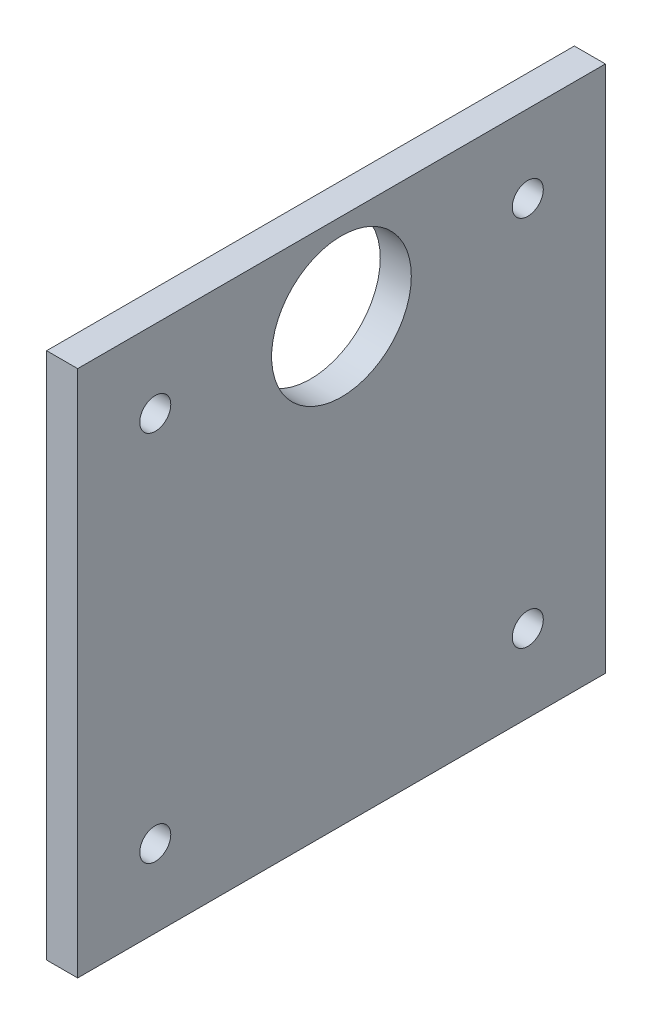
SolidWorks part; units mm, degrees
material "1060 Alloy"
ref_plane "Front Plane" through (0, 0, 0) normal (0, 0, 1) x (1, 0, 0)
ref_plane "Top Plane" through (0, 0, 0) normal (0, 1, 0) x (1, 0, 0)
ref_plane "Right Plane" through (0, 0, 0) normal (1, 0, 0) x (0, 0, -1)
sketch "Sketch1" plane through (0, 0, 0) normal (1, 0, 0) x (0, 0, -1)
  line L1 (-53.975, -53.975) -> (53.975, -53.975)
  line L2 (-53.975, -53.975) -> (-53.975, 53.975)
  line L3 (-53.975, 53.975) -> (53.975, 53.975)
  line L4 (53.975, -53.975) -> (53.975, 53.975)
  line L5 (-53.975, -53.975) -> (53.975, 53.975) construction
  line L6 (-53.975, 53.975) -> (53.975, -53.975) construction
  circle A0 centre (-0.0121, 36.2388) radius 14.2875
  circle A1 centre (-38.1, 38.1) radius 3.175
  circle A2 centre (38.1, 38.1) radius 3.175
  circle A3 centre (38.1, -38.1) radius 3.175
  circle A4 centre (-38.1, -38.1) radius 3.175
  point P0 (0, 0)
  dimension "D2" = 28.575
  dimension "D3" = 6.35
  dimension "D1" = 107.95
extrude "Boss-Extrude1" add sketch "Sketch1" along normal mid plane 6.35
